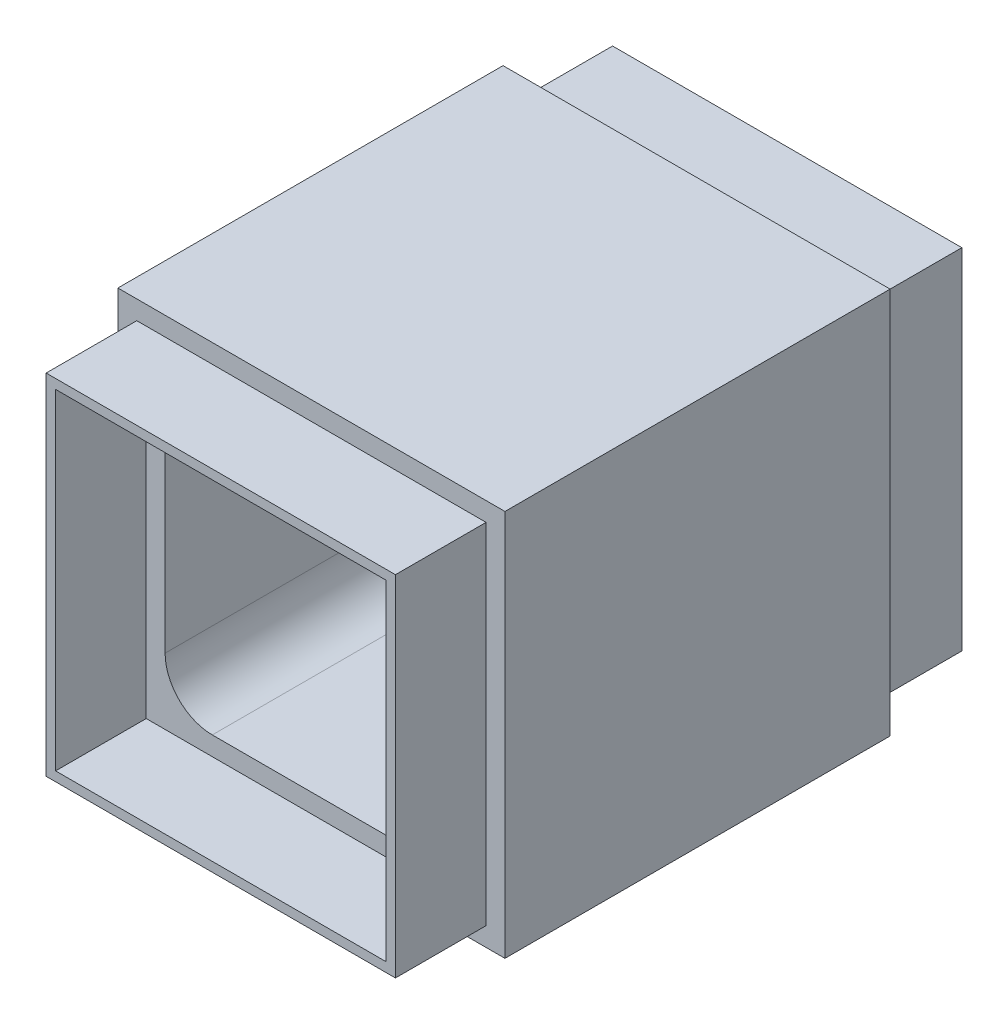
SolidWorks part; units mm, degrees
ref_plane "Front Plane" through (0, 0, 0) normal (0, 0, 1) x (1, 0, 0)
ref_plane "Top Plane" through (0, 0, 0) normal (0, 1, 0) x (1, 0, 0)
ref_plane "Right Plane" through (0, 0, 0) normal (1, 0, 0) x (0, 0, -1)
sketch "Sketch1" plane through (0, 0, 0) normal (0, 0, 1) x (1, 0, 0)
  line L1 (0, 0) -> (52.07, 0)
  line L2 (0, 0) -> (0, 52.07)
  line L3 (0, 52.07) -> (52.07, 52.07)
  line L4 (52.07, 0) -> (52.07, 52.07)
  dimension "D1" = 52.07
  dimension "D2" = 52.07
extrude "Boss-Extrude1" add sketch "Sketch1" against normal blind 76.2
sketch "Sketch2" plane through (0, 0, 0) normal (0, 0, 1) x (1, 0, 0)
  line L0 (0, 52.07) -> (0, 0) construction
  line L1 (6.35, 45.72) -> (45.72, 45.72)
  line L2 (6.35, 45.72) -> (6.35, 6.35)
  line L3 (6.35, 6.35) -> (45.72, 6.35)
  line L4 (45.72, 45.72) -> (45.72, 6.35)
  line L5 (0, 0) -> (52.07, 0) construction
  line L6 (52.07, 0) -> (52.07, 52.07) construction
  line L7 (52.07, 52.07) -> (0, 52.07) construction
  dimension "D1" = 6.35
  dimension "D2" = 6.35
  dimension "D3" = 6.35
  dimension "D4" = 6.35
extrude "Cut-Extrude1" cut sketch "Sketch2" against normal through all
sketch "Sketch3" plane through (0, 0, 0) normal (0, 0, 1) x (1, 0, 0)
  line L0 (0, 52.07) -> (0, 0) construction
  line L1 (2.54, 49.53) -> (49.53, 49.53)
  line L2 (2.54, 49.53) -> (2.54, 2.54)
  line L3 (2.54, 2.54) -> (49.53, 2.54)
  line L4 (49.53, 49.53) -> (49.53, 2.54)
  line L5 (52.07, 0) -> (52.07, 52.07) construction
  line L6 (0, 0) -> (52.07, 0) construction
  line L7 (52.07, 52.07) -> (0, 52.07) construction
  line L9 (3.81, 48.26) -> (48.26, 48.26)
  line L10 (3.81, 48.26) -> (3.81, 3.81)
  line L11 (3.81, 3.81) -> (48.26, 3.81)
  line L12 (48.26, 48.26) -> (48.26, 3.81)
  line M9 (45.72, 6.35) -> (6.35, 6.35)
  line M10 (6.35, 6.35) -> (6.35, 45.72)
  line M11 (6.35, 45.72) -> (45.72, 45.72)
  line M12 (45.72, 45.72) -> (45.72, 6.35)
  line M13 (0, 52.07) -> (0, 0)
  line M14 (0, 0) -> (52.07, 0)
  line M15 (52.07, 0) -> (52.07, 52.07)
  line M16 (52.07, 52.07) -> (0, 52.07)
  dimension "D1" = 2.54
  dimension "D2" = 2.54
  dimension "D3" = 2.54
  dimension "D4" = 2.54
  dimension "D5" = 1.27
  dimension "D6" = 1.27
  dimension "D7" = 1.27
  dimension "D8" = 1.27
extrude "Cut-Extrude2" cut sketch "Sketch3" against normal blind 12.192 contours L1 L4 L3 L2 M16 M13 M14 M15 | L12 L9 L10 L11 M12 M9 M10 M11 region at (26.035, 47.6314, 0) region at (26.035, 51.3336, 0)
ref_plane "Plane1" through (0, 0, -38.1) normal (0, 0, -1) x (-1, 0, 0)
mirror "Mirror1" about plane through (0, 0, -38.1) normal (0, 0, -1) of "Cut-Extrude2"
fillet "Fillet1" radius 6.35 4 edges at (6.35, 45.72, -38.1) (45.72, 45.72, -38.1) (45.72, 6.35, -38.1) (6.35, 6.35, -38.1)
